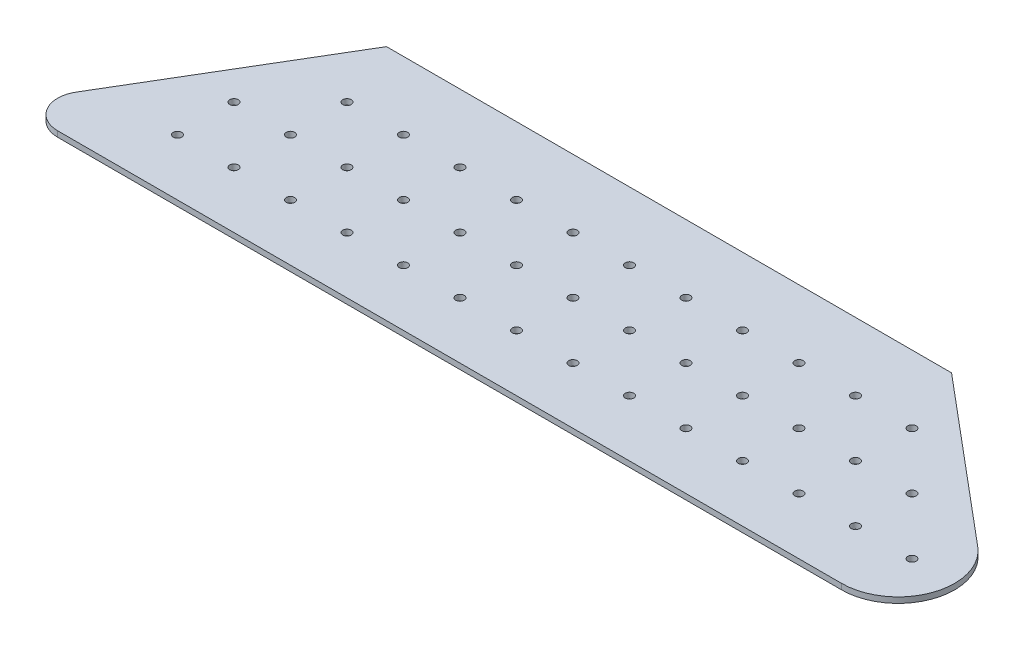
SolidWorks part; units mm, degrees
ref_plane "Front Plane" through (0, 0, 0) normal (0, 0, 1) x (1, 0, 0)
ref_plane "Top Plane" through (0, 0, 0) normal (0, 1, 0) x (1, 0, 0)
ref_plane "Right Plane" through (0, 0, 0) normal (1, 0, 0) x (0, 0, -1)
sketch "Sketch1" plane through (0, 0, 0) normal (0, 1, 0) x (1, 0, 0)
  line L0 (-17.984, 0) -> (332.016, 0)
  line L1 (-55, 0) -> (55, 0) construction
  line L2 (332.016, 0) -> (232.016, 84)
  line L3 (232.016, 84) -> (32.016, 84)
  line L4 (32.016, 84) -> (-17.984, 0)
  line L5 (-45.5557, 20) -> (286.5842, 20) construction
  line L6 (-34.9172, 40) -> (80.516, 40) construction
  line L7 (-27.9699, 60) -> (20.516, 60) construction
  line L8 (308.2064, 20) -> (439.4037, 20) construction
  line L9 (123.516, 40) -> (160.516, 40) construction
  line L10 (163.516, 40) -> (200.516, 40) construction
  line L11 (203.516, 40) -> (233.588, 40) construction
  line L12 (236.588, 40) -> (263.1596, 40) construction
  line L13 (266.1596, 40) -> (280.516, 40) construction
  line L14 (236.588, 60) -> (319.174, 60) construction
  line L15 (203.516, 60) -> (233.588, 60) construction
  line L16 (163.516, 60) -> (200.516, 60) construction
  line L17 (123.516, 60) -> (160.516, 60) construction
  line L18 (83.516, 60) -> (120.516, 60) construction
  line L19 (43.516, 60) -> (80.516, 60) construction
  line L20 (83.516, 40) -> (120.516, 40) construction
  line L21 (242.016, 20) -> (242.016, 12.284) construction
  line L22 (76.4385, 30) -> (108.1697, 30) construction
  line L23 (283.516, 40) -> (434.9926, 40) construction
  circle A0 centre (42.016, 20) radius 1.5
  circle A1 centre (62.016, 20) radius 1.5
  circle A2 centre (82.016, 20) radius 1.5
  circle A3 centre (102.016, 20) radius 1.5
  circle A4 centre (122.016, 20) radius 1.5
  circle A21 centre (22.016, 20) radius 1.5
  circle A22 centre (162.016, 20) radius 1.5
  circle A23 centre (182.016, 20) radius 1.5
  circle A24 centre (202.016, 20) radius 1.5
  circle A25 centre (222.016, 20) radius 1.5
  circle A26 centre (242.016, 20) radius 1.5
  circle A27 centre (142.016, 20) radius 1.5
  circle A28 centre (242.016, 60) radius 1.5
  circle A29 centre (222.016, 60) radius 1.5
  circle A30 centre (202.016, 60) radius 1.5
  circle A31 centre (182.016, 60) radius 1.5
  circle A32 centre (162.016, 60) radius 1.5
  circle A33 centre (142.016, 60) radius 1.5
  circle A34 centre (122.016, 60) radius 1.5
  circle A35 centre (102.016, 60) radius 1.5
  circle A36 centre (82.016, 60) radius 1.5
  circle A37 centre (62.016, 60) radius 1.5
  circle A38 centre (42.016, 60) radius 1.5
  circle A41 centre (282.016, 20) radius 1.5
  circle A42 centre (262.016, 20) radius 1.5
  circle A44 centre (262.016, 40) radius 1.5
  circle A45 centre (242.016, 40) radius 1.5
  circle A46 centre (202.016, 40) radius 1.5
  circle A47 centre (182.016, 40) radius 1.5
  circle A48 centre (162.016, 40) radius 1.5
  circle A49 centre (142.016, 40) radius 1.5
  circle A50 centre (122.016, 40) radius 1.5
  circle A51 centre (102.016, 40) radius 1.5
  circle A52 centre (82.016, 40) radius 1.5
  circle A53 centre (62.016, 40) radius 1.5
  circle A54 centre (42.016, 40) radius 1.5
  circle A55 centre (22.016, 40) radius 1.5
  circle A56 centre (222.016, 40) radius 1.5
  dimension "D13" = 3
  dimension "D14" = 3
  dimension "D15" = 3
  dimension "D16" = 3
  dimension "D17" = 3
  dimension "D18" = 20
  dimension "D19" = 10
  dimension "D20" = 40
  dimension "D21" = 60
  dimension "D22" = 80
  dimension "D23" = 100
  dimension "D24" = 20
  dimension "D25" = 0
  dimension "D28" = 3
  dimension "D34" = 20
  dimension "D1" = 350
  dimension "D2" = 84
  dimension "D3" = 100
  dimension "D4" = 200
  dimension "D5" = 20
  dimension "D6" = 40
  dimension "D7" = 60
  dimension "D8" = 60
  dimension "D9" = 80
  dimension "D10" = 100
  dimension "D11" = 120
  dimension "D12" = 140
extrude "Boss-Extrude1" add sketch "Sketch1" along normal blind 2
fillet "Fillet4" radius 20 1 edges at (332.016, 1, 0)
fillet "Fillet5" radius 10 1 edges at (-17.984, 1, 0)
